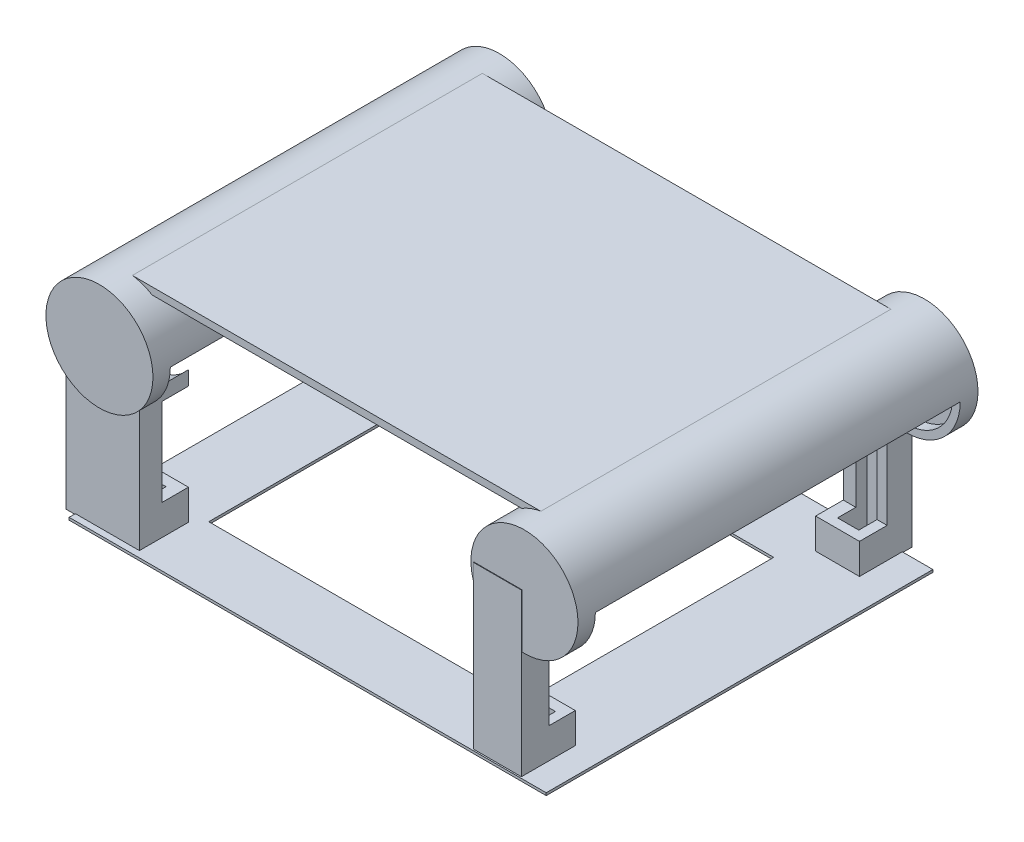
SolidWorks part; units mm, degrees
ref_plane "Front Plane" through (0, 0, 0) normal (0, 0, 1) x (1, 0, 0)
ref_plane "Top Plane" through (0, 0, 0) normal (0, 1, 0) x (1, 0, 0)
ref_plane "Right Plane" through (0, 0, 0) normal (1, 0, 0) x (0, 0, -1)
sketch "MotorHoldersSketch" plane through (0, 0, 0) normal (0, 0, 1) x (1, 0, 0)
  line L0 (0, 0) -> (170, 0) construction
  line L1 (0, 0) -> (0, 21.41) construction
  line L2 (170, 0) -> (170, 21.41) construction
  circle A0 centre (0, 0) radius 21.41
  circle A1 centre (170, 0) radius 21.41
ref_axis "Axis1" through (0, 0, 0) along (0, 0, 1)
ref_axis "Axis2" through (170, 0, 0) along (0, 0, 1)
extrude "MotorHolders" add sketch "MotorHoldersSketch" along normal blind 80 and the other way blind 80
sketch "Sketch3" plane through (0, 0, 0) normal (0, 0, 1) x (1, 0, 0)
  line L1 (1.9406, 21.133) -> (168.3435, 21.133)
  line L2 (1.9406, 21.133) -> (1.9406, 18.3155)
  line L3 (1.9406, 18.3155) -> (168.3435, 18.3155)
  line L4 (168.3435, 21.133) -> (168.3435, 18.3155)
extrude "Boss-Extrude2" add sketch "Sketch3" along normal blind 70 and the other way blind 70
sketch "Sketch4" plane through (0, 0, 0) normal (0, 1, 0) x (1, 0, 0)
  line L1 (221.2811, -73.0508) -> (-41.4939, -73.0508)
  line L2 (221.2811, -73.0508) -> (221.2811, 72.8691)
  line L3 (221.2811, 72.8691) -> (-41.4939, 72.8691)
  line L4 (-41.4939, -73.0508) -> (-41.4939, 72.8691)
extrude "Cut-Extrude1" cut sketch "Sketch4" against normal blind 23
ref_axis "Axis3" through (170, 0, 0) along (0, -1, 0)
sketch3d "3DSketch1"
  line L0 (170, 0, 0) -> (170, -34.8293, 0)
  line L1 (170, 0, 0) -> (170, -38.994, 0) construction
ref_plane "Plane1" through (170, -34.8293, 0) normal (0, -1, 0) x (-1, 0, 0)
sketch "Sketch6" plane through (170, -34.8293, 0) normal (0, -1, 0) x (-1, 0, 0)
  line L1 (185.651, 78.949) -> (154.5717, 78.949)
  line L2 (185.651, 78.949) -> (185.651, 56.3099)
  line L3 (185.651, 56.3099) -> (154.5717, 56.3099)
  line L4 (154.5717, 78.949) -> (154.5717, 56.3099)
  line L5 (185.1605, -58.6712) -> (155.7267, -58.6712)
  line L6 (185.1605, -58.6712) -> (185.1605, -78.2822)
  line L7 (185.1605, -78.2822) -> (155.7267, -78.2822)
  line L8 (155.7267, -58.6712) -> (155.7267, -78.2822)
  line L9 (20.2985, 77.8627) -> (2.7559, 77.8627)
  line L10 (20.2985, 77.8627) -> (20.2985, 56.7633)
  line L11 (20.2985, 56.7633) -> (2.7559, 56.7633)
  line L12 (2.7559, 77.8627) -> (2.7559, 56.7633)
  line L13 (20.1677, -58.6712) -> (1.0007, -58.6712)
  line L14 (20.1677, -58.6712) -> (20.1677, -80.2189)
  line L15 (20.1677, -80.2189) -> (1.0007, -80.2189)
  line L16 (1.0007, -58.6712) -> (1.0007, -80.2189)
  line L17 (180.4665, 72.2461) -> (157.7696, 72.2461)
  line L18 (180.4665, 72.2461) -> (180.4665, 60.5121)
  line L19 (180.4665, 60.5121) -> (157.7696, 60.5121)
  line L20 (157.7696, 72.2461) -> (157.7696, 60.5121)
  line L21 (15.2746, 72.2461) -> (6.7922, 72.2461)
  line L22 (15.2746, 72.2461) -> (15.2746, 60.5121)
  line L23 (15.2746, 60.5121) -> (6.7922, 60.5121)
  line L24 (6.7922, 72.2461) -> (6.7922, 60.5121)
  line L25 (15.2746, -72.8101) -> (4.6276, -72.8101)
  line L26 (15.2746, -72.8101) -> (15.2746, -62.9794)
  line L27 (15.2746, -62.9794) -> (4.6276, -62.9794)
  line L28 (4.6276, -72.8101) -> (4.6276, -62.9794)
  line L29 (180.4665, -72.8101) -> (160.3766, -72.8101)
  line L30 (180.4665, -72.8101) -> (180.4665, -62.9794)
  line L31 (180.4665, -62.9794) -> (160.3766, -62.9794)
  line L32 (160.3766, -72.8101) -> (160.3766, -62.9794)
extrude "PowerBankHolders" add sketch "Sketch6" along normal blind 30 and the other way blind 35 separate body
sketch3d "3DSketch3"
  line L0 (170, 0, 0) -> (170, -64.5, 0) construction
ref_plane "Plane2" through (170, -64.5, 0) normal (0, -1, 0) x (-1, 0, 0)
sketch "Sketch7" plane through (170, -64.5, 0) normal (0, -1, 0) x (-1, 0, 0)
  line L1 (-9.5047, -80.801) -> (181.32, -80.801)
  line L2 (-9.5047, -80.801) -> (-9.5047, 73.8662)
  line L3 (-9.5047, 73.8662) -> (181.32, 73.8662)
  line L4 (181.32, -80.801) -> (181.32, 73.8662)
  line L5 (151.8712, -54.3972) -> (26.5361, -54.3972)
  line L6 (151.8712, -54.3972) -> (151.8712, 46.2413)
  line L7 (151.8712, 46.2413) -> (26.5361, 46.2413)
  line L8 (26.5361, -54.3972) -> (26.5361, 46.2413)
extrude "TopCellPhoneCover" add sketch "Sketch7" along normal blind 1
sketch "Sketch9" plane through (170, -34.8293, 0) normal (0, -1, 0) x (-1, 0, 0)
  line L1 (183.1646, -69.1826) -> (-59.9818, -69.1826)
  line L2 (183.1646, -69.1826) -> (183.1646, 67.8174)
  line L3 (183.1646, 67.8174) -> (-59.9818, 67.8174)
  line L4 (-59.9818, -69.1826) -> (-59.9818, 67.8174)
extrude "PowerBankExtrude" cut sketch "Sketch9" along normal blind 17.5 and the other way blind 17.5
ref_point "Point1"
ref_point "Point2"
sketch3d "3DSketch11"
  line L0 (0, 0, -80) -> (170, 0, 80) construction
  point P4 (85, 0, 0)
sketch "MotorHolderExtrudeSketch" plane through (0, 0, 0) normal (0, 0, 1) x (1, 0, 0)
  circle A0 centre (170, 0) radius 18.415
  circle A1 centre (0, 0) radius 18.415
  circle A3 centre (0, 0) radius 21.41 construction
  circle A4 centre (170, 0) radius 21.41 construction
extrude "MotorHolderExtrude" cut sketch "MotorHolderExtrudeSketch" against normal blind 77 and the other way blind 77
